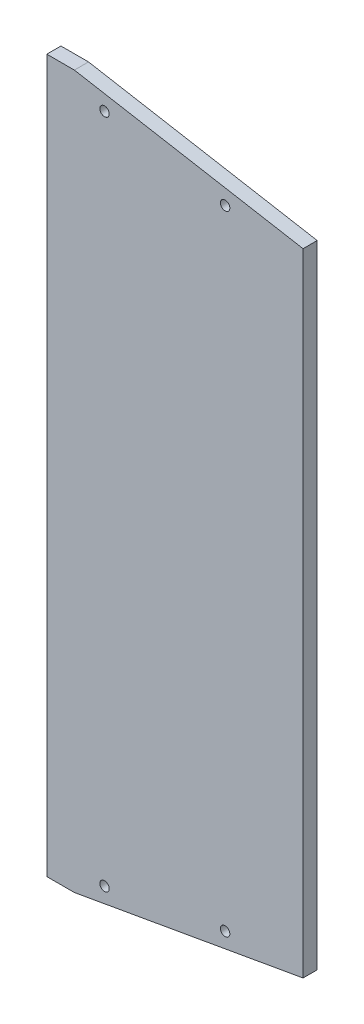
SolidWorks part; units mm, degrees
material "Pine"
ref_plane "Front Plane" through (0, 0, 0) normal (0, 0, 1) x (1, 0, 0)
ref_plane "Top Plane" through (0, 0, 0) normal (0, 1, 0) x (1, 0, 0)
ref_plane "Right Plane" through (0, 0, 0) normal (1, 0, 0) x (0, 0, -1)
sketch "Sketch1" plane through (0, 0, 0) normal (0, 0, 1) x (1, 0, 0)
  line L0 (151.0236, 152.5404) -> (-41.6441, 186.5129)
  line L1 (-64.8764, 186.5129) -> (-41.6441, 186.5129)
  line L2 (-64.8764, 186.5129) -> (-64.8764, -413.5621)
  line L3 (-64.8764, -413.5621) -> (-41.6441, -413.5621)
  line L4 (151.0236, 152.5404) -> (151.0236, -379.5896)
  line L5 (151.0236, -113.5246) -> (-64.8764, -113.5246) construction
  line L6 (151.0236, -379.5896) -> (-41.6441, -413.5621)
  dimension "D1" = 532.13
  dimension "D2" = 215.9
  dimension "D3" = 170
  dimension "D4" = 600.075
extrude "Boss-Extrude1" add sketch "Sketch1" along normal blind 11.9062
hole_wizard "5/16 (0.3125) Diameter Hole1" positions "Sketch2" profile "Sketch3" hole size "5/16" standard "ANSI Inch" end condition through all
sketch "Sketch2" plane through (0, 0, 11.9062) normal (0, 0, 1) x (1, 0, 0)
  line L0 (151.0236, 152.5404) -> (-41.6441, 186.5129) construction
  line L1 (-41.6441, -413.5621) -> (151.0236, -379.5896) construction
  point P0 (85.3559, 151.2234)
  point P2 (-16.2441, 169.1383)
  point P4 (-16.2441, -396.1875)
  point P6 (85.3559, -378.2727)
  dimension "D1" = 12.7
  dimension "D2" = 12.7
  dimension "D3" = 12.7
  dimension "D4" = 12.7
  dimension "D5" = 101.6
  dimension "D6" = 25.4
sketch "Sketch3" plane through (85.3559, 151.2234, 11.9062) normal (1, 0, 0) x (0, -1, 0)
  line L0 (0, 0) -> (0, 11.9062)
  line L1 (0, 11.9062) -> (3.9687, 11.9062)
  line L2 (3.9687, 11.9062) -> (3.9687, 0)
  line L5 (3.9687, 0) -> (0, 0)
  line L11 (0, -6.35) -> (0, 107.95) construction
  dimension "Thru Hole Dia." = 7.9375
  dimension "Thru Hole Depth" = 11.9062
